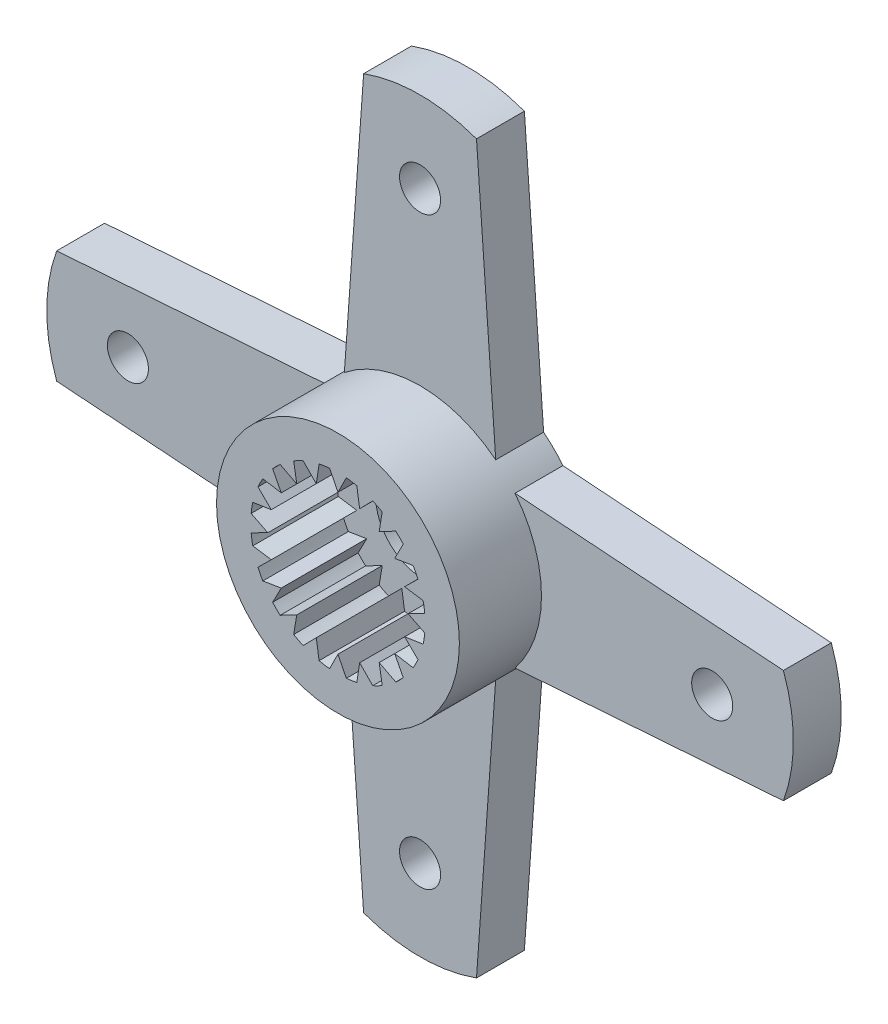
SolidWorks part; units mm, degrees
ref_plane "Front Plane" through (0, 0, 0) normal (0, 0, 1) x (1, 0, 0)
ref_plane "Top Plane" through (0, 0, 0) normal (0, 1, 0) x (1, 0, 0)
ref_plane "Right Plane" through (0, 0, 0) normal (1, 0, 0) x (0, 0, -1)
sketch "Sketch2" plane through (0, 0, 0) normal (0, 0, 1) x (1, 0, 0)
  circle A0 centre (0, 0) radius 3.55
  dimension "D1" = 7.1
sketch "Sketch3" plane through (0, 0, 0) normal (0, 0, 1) x (1, 0, 0)
  line L0 (-0.2447, 2.5382) -> (0, 2.05)
  line L1 (0, 2.05) -> (0.2447, 2.5382)
  line L2 (0.5516, 2.4896) -> (0.6335, 1.9497)
  line L3 (0.6335, 1.9497) -> (1.0171, 2.3384)
  line L4 (1.294, 2.1973) -> (1.205, 1.6585)
  line L5 (1.205, 1.6585) -> (1.6899, 1.9096)
  line L6 (1.9096, 1.6899) -> (1.6585, 1.205)
  line L7 (1.6585, 1.205) -> (2.1973, 1.294)
  line L8 (2.3384, 1.0171) -> (1.9497, 0.6335)
  line L9 (1.9497, 0.6335) -> (2.4896, 0.5516)
  line L10 (2.5382, 0.2447) -> (2.05, 0)
  line L11 (2.05, 0) -> (2.5382, -0.2447)
  line L12 (2.4896, -0.5516) -> (1.9497, -0.6335)
  line L13 (1.9497, -0.6335) -> (2.3384, -1.0171)
  line L14 (2.1973, -1.294) -> (1.6585, -1.205)
  line L15 (1.6585, -1.205) -> (1.9096, -1.6899)
  line L16 (1.6899, -1.9096) -> (1.205, -1.6585)
  line L17 (1.205, -1.6585) -> (1.294, -2.1973)
  line L18 (1.0171, -2.3384) -> (0.6335, -1.9497)
  line L19 (0.6335, -1.9497) -> (0.5516, -2.4896)
  line L20 (0.2447, -2.5382) -> (0, -2.05)
  line L21 (0, -2.05) -> (-0.2447, -2.5382)
  line L22 (-0.5516, -2.4896) -> (-0.6335, -1.9497)
  line L23 (-0.6335, -1.9497) -> (-1.0171, -2.3384)
  line L24 (-1.294, -2.1973) -> (-1.205, -1.6585)
  line L25 (-1.205, -1.6585) -> (-1.6899, -1.9096)
  line L26 (-1.9096, -1.6899) -> (-1.6585, -1.205)
  line L27 (-1.6585, -1.205) -> (-2.1973, -1.294)
  line L28 (-2.3384, -1.0171) -> (-1.9497, -0.6335)
  line L29 (-1.9497, -0.6335) -> (-2.4896, -0.5516)
  line L30 (-2.5382, -0.2447) -> (-2.05, 0)
  line L31 (-2.05, 0) -> (-2.5382, 0.2447)
  line L32 (-2.4896, 0.5516) -> (-1.9497, 0.6335)
  line L33 (-1.9497, 0.6335) -> (-2.3384, 1.0171)
  line L34 (-2.1973, 1.294) -> (-1.6585, 1.205)
  line L35 (-1.6585, 1.205) -> (-1.9096, 1.6899)
  line L36 (-1.6899, 1.9096) -> (-1.205, 1.6585)
  line L37 (-1.205, 1.6585) -> (-1.294, 2.1973)
  line L38 (-1.0171, 2.3384) -> (-0.6335, 1.9497)
  line L39 (-0.6335, 1.9497) -> (-0.5516, 2.4896)
  arc A0 (-0.2447, 2.5382) -> (0.2447, 2.5382) centre (0, 0) cw
  arc A2 (0.5516, 2.4896) -> (1.0171, 2.3384) centre (0, 0) cw
  arc A3 (1.294, 2.1973) -> (1.6899, 1.9096) centre (0, 0) cw
  arc A4 (1.9096, 1.6899) -> (2.1973, 1.294) centre (0, 0) cw
  arc A5 (2.3384, 1.0171) -> (2.4896, 0.5516) centre (0, 0) cw
  arc A6 (2.5382, 0.2447) -> (2.5382, -0.2447) centre (0, 0) cw
  arc A7 (2.4896, -0.5516) -> (2.3384, -1.0171) centre (0, 0) cw
  arc A8 (2.1973, -1.294) -> (1.9096, -1.6899) centre (0, 0) cw
  arc A9 (1.6899, -1.9096) -> (1.294, -2.1973) centre (0, 0) cw
  arc A10 (1.0171, -2.3384) -> (0.5516, -2.4896) centre (0, 0) cw
  arc A11 (0.2447, -2.5382) -> (-0.2447, -2.5382) centre (0, 0) cw
  arc A12 (-0.5516, -2.4896) -> (-1.0171, -2.3384) centre (0, 0) cw
  arc A13 (-1.294, -2.1973) -> (-1.6899, -1.9096) centre (0, 0) cw
  arc A14 (-1.9096, -1.6899) -> (-2.1973, -1.294) centre (0, 0) cw
  arc A15 (-2.3384, -1.0171) -> (-2.4896, -0.5516) centre (0, 0) cw
  arc A16 (-2.5382, -0.2447) -> (-2.5382, 0.2447) centre (0, 0) cw
  arc A17 (-2.4896, 0.5516) -> (-2.3384, 1.0171) centre (0, 0) cw
  arc A18 (-2.1973, 1.294) -> (-1.9096, 1.6899) centre (0, 0) cw
  arc A19 (-1.6899, 1.9096) -> (-1.294, 2.1973) centre (0, 0) cw
  arc A20 (-1.0171, 2.3384) -> (-0.5516, 2.4896) centre (0, 0) cw
  point P66 (0, 0)
  dimension "D1" = 20
ref_plane "Plane1" through (0, 0, -2.4) normal (0, 0, 1) x (1, 0, 0)
sketch "Sketch4" plane through (0, 0, -2.4) normal (0, 0, 1) x (1, 0, 0)
  line L0 (2.7764, 2.2123) -> (10.6226, 1.65)
  line L1 (2.7764, -2.2123) -> (10.6226, -1.65)
  arc A0 (10.6226, 1.65) -> (10.6226, -1.65) centre (6.0891, 0) cw
  arc A1 (2.7764, 2.2123) -> (2.7764, -2.2123) centre (0, 0) cw
extrude "Boss-Extrude1" add sketch "Sketch2" against normal blind 3.8 contours A0
extrude "Boss-Extrude2" add sketch "Sketch4" against normal blind 1.4
sketch "Sketch5" plane through (0, 0, 0) normal (0, 0, 1) x (1, 0, 0)
  circle A0 centre (0, 0) radius 2.55
extrude "Cut-Extrude1" cut sketch "Sketch5" against normal blind 2.5
extrude "Boss-Extrude3" add sketch "Sketch3" against normal up to surface (2.5 mm away) up to face at (2.55, 0, -2.5)
sketch "Sketch6" plane through (0, 0, -2.5) normal (0, 0, 1) x (1, 0, 0)
  circle A0 centre (0, 0) radius 1.4
  dimension "D1" = 2.8
extrude "Cut-Extrude2" cut sketch "Sketch6" against normal through all
sketch "Sketch7" plane through (0, 0, -2.4) normal (0, 0, 1) x (1, 0, 0)
  circle A0 centre (8.5405, 0) radius 0.6
  dimension "D1" = 1.2
extrude "Cut-Extrude3" cut sketch "Sketch7" against normal through all
pattern_circular "CirPattern1" count 4 over 360 about axis through (0, 0, -2.5) along (0, 0, 1) of "Boss-Extrude2"
pattern_circular "CirPattern2" count 4 over 360 about axis through (0, 0, -2.5) along (0, 0, 1) of "Cut-Extrude3"
